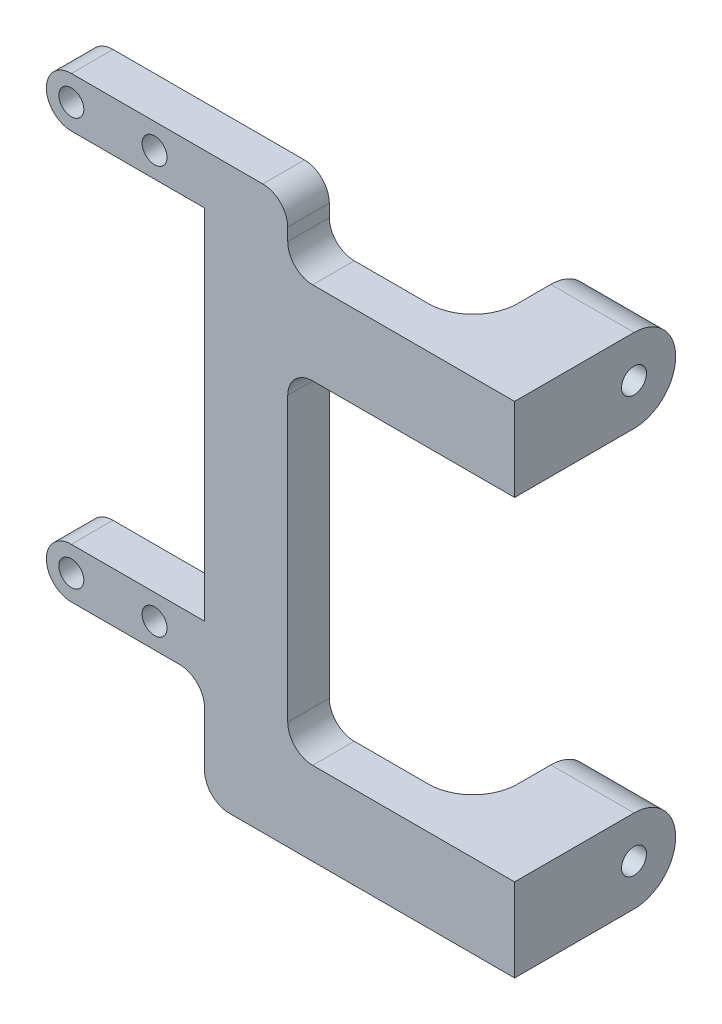
SolidWorks part; units mm, degrees
ref_plane "前视基准面" through (0, 0, 0) normal (0, 0, 1) x (1, 0, 0)
ref_plane "上视基准面" through (0, 0, 0) normal (0, 1, 0) x (1, 0, 0)
ref_plane "右视基准面" through (0, 0, 0) normal (1, 0, 0) x (0, 0, -1)
sketch "草图1" plane through (0, 0, 0) normal (0, 0, 1) x (1, 0, 0)
  line L4 (-3, 37.5) -> (-3, 31.5)
  line L5 (-3, 31.5) -> (16, 31.5)
  line L7 (-3, -17.5) -> (-3, -11.5)
  line L10 (16, 31.5) -> (16, -11.5)
  line L11 (16, -11.5) -> (-3, -11.5)
  line L12 (26, 30) -> (53.26, 30)
  line L13 (26, 20) -> (53.26, 20)
  line L14 (26, -20) -> (53.26, -20)
  line L15 (26, -30) -> (53.26, -30)
  line L16 (-3, 37.5) -> (26, 37.5)
  line L17 (53.26, 30) -> (53.26, 20)
  line L18 (53.26, -20) -> (53.26, -30)
  line L19 (26, -30) -> (16, -30)
  line L20 (16, -30) -> (16, -17.5)
  line L21 (26, -17.5) -> (26, -20)
  line L22 (16, -17.5) -> (-3, -17.5)
  line L23 (26, 37.5) -> (26, 30)
  line L24 (26, 20) -> (26, -17.5)
  circle A0 centre (0, -14.5) radius 1.5
  circle A1 centre (0, 34.5) radius 1.5
  circle A2 centre (10, 34.5) radius 1.5
  circle A4 centre (10, -14.5) radius 1.5
extrude "凸台-拉伸1" add sketch "草图1" along normal blind 5
fillet "圆角1" radius 3 10 edges at (26, 20, 2.5) (26, -20, 2.5) (26, 30, 2.5) (26, 37.5, 2.5) (16, -30, 2.5) (16, -17.5, 2.5) (-3, -17.5, 2.5) (-3, -11.5, 2.5) (-3, 37.5, 2.5) (-3, 31.5, 2.5)
sketch "草图2" plane through (53.26, 0, 0) normal (1, 0, 0) x (0, 0, -1)
  line L0 (0, 30) -> (14.35, 30)
  line L1 (0, 30) -> (0, 20)
  line L2 (0, 20) -> (14.35, 20)
  line L3 (14.35, 20) -> (14.35, 30)
  line L4 (0, -20) -> (14.35, -20)
  line L5 (14.35, -20) -> (14.35, -30)
  line L6 (14.35, -30) -> (0, -30)
  line L7 (0, -30) -> (0, -20)
  circle A0 centre (9.35, 25) radius 1.5
  circle A1 centre (9.35, -25) radius 1.5
  point P16 (0, 0)
  point P17 (0, 0)
  point P18 (0, 0)
  point P19 (0, 0)
extrude "凸台-拉伸2" add sketch "草图2" against normal blind 10
fillet "圆角2" radius 5 4 edges at (48.26, 30, -14.35) (48.26, 20, -14.35) (48.26, -20, -14.35) (48.26, -30, -14.35)
fillet "圆角4" radius 5.35 2 edges at (43.26, -25, 0) (43.26, 25, 0)
